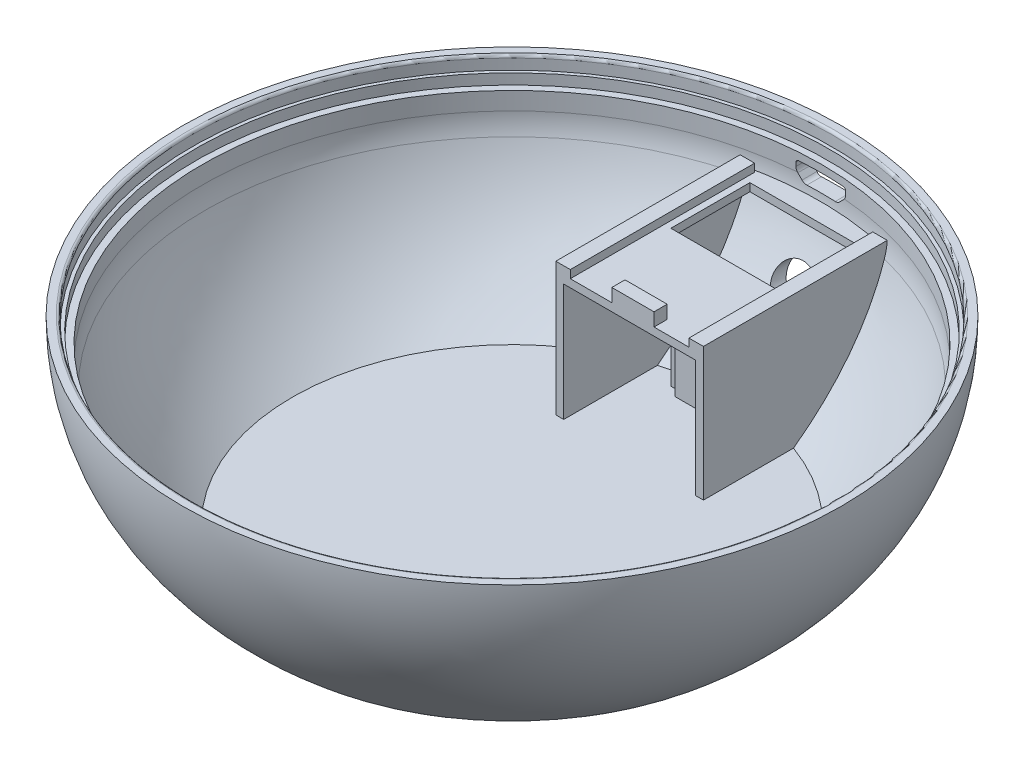
SolidWorks part; units mm, degrees
ref_plane "Plano frontal" through (0, 0, 0) normal (0, 0, 1) x (1, 0, 0)
ref_plane "Plano superior" through (0, 0, 0) normal (0, 1, 0) x (1, 0, 0)
ref_plane "Plano direito" through (0, 0, 0) normal (1, 0, 0) x (0, 0, -1)
sketch "Esboço1" plane through (0, 0, 0) normal (0, 0, 1) x (1, 0, 0)
  line L0 (0, 0) -> (0, -29.3333)
  line L1 (33.9935, -29.3333) -> (0, -29.3333)
  line L4 (0, 0) -> (50, 0)
  ellipse E0 centre (0, 0) end of major axis (-50, 0) minor radius 40 (33.9935, -29.3333) -> (50, 0) ccw
  dimension "D1" = 40
  dimension "D2" = 100
  dimension "D3" = 33.9935
revolve "Revolução1" add sketch "Esboço1" angle 360 about L0
shell "Casca1" thickness 2 removed face at (0, 0, 50)
sketch "Esboço7" plane through (0, 0, 0) normal (0, 1, 0) x (1, 0, 0)
  circle A0 centre (0, 0) radius 47
  circle A1 centre (0, 0) radius 48
  dimension "D1" = 94
extrude "Ressalto-extrusão3" add sketch "Esboço7" against normal up to next
sketch "Esboço9" plane through (0, 0, 0) normal (0, 1, 0) x (1, 0, 0)
  circle A0 centre (0, 0) radius 48.5
  dimension "D1" = 97
extrude "Corte-extrusão5" cut sketch "Esboço9" against normal blind 2
fillet "Filete3" radius 10 1 edges at (0, -7.7061, 47)
fillet "Filete4" radius 0.4 1 edges at (0, 0, 48.5)
fillet "Filete9" radius 6 1 edges at (0, -29.3333, 33.9935)
sketch "Esboço10" plane through (0, -2, 0) normal (0, 1, 0) x (1, 0, 0)
  circle A0 centre (0, 0) radius 48
  dimension "D1" = 96
extrude "Corte-extrusão6" cut sketch "Esboço10" against normal blind 1.6
sketch "Esboço15" plane through (0, 0, 0) normal (0, 0, 1) x (1, 0, 0)
  line L0 (0, -7.3333) -> (0, -4.7333) construction
  line L2 (-3.375, -4.7333) -> (3.375, -4.7333)
  line L3 (3.775, -5.1333) -> (3.775, -5.681)
  line L4 (3.4964, -6.3736) -> (2.8702, -7.0259)
  line L5 (2.1488, -7.3333) -> (-2.1488, -7.3333)
  line L6 (33.3248, -27.3333) -> (-33.3248, -27.3333) construction
  line L7 (-3.4964, -6.3736) -> (-2.8702, -7.0259)
  line L8 (-3.775, -5.1333) -> (-3.775, -5.681)
  arc A0 (2.8702, -7.0259) -> (2.1488, -7.3333) centre (2.1488, -6.3333) cw
  arc A1 (-2.8702, -7.0259) -> (-2.1488, -7.3333) centre (-2.1488, -6.3333) ccw
  arc A2 (3.775, -5.681) -> (3.4964, -6.3736) centre (2.775, -5.681) cw
  arc A3 (-3.4964, -6.3736) -> (-3.775, -5.681) centre (-2.775, -5.681) cw
  arc A4 (3.375, -4.7333) -> (3.775, -5.1333) centre (3.375, -5.1333) cw
  arc A5 (-3.775, -5.1333) -> (-3.375, -4.7333) centre (-3.375, -5.1333) cw
  point P14 (2.575, -7.3333)
  point P17 (-2.575, -7.3333)
  point P20 (3.775, -6.0833)
  point P23 (-3.775, -6.0833)
  point P26 (3.775, -4.7333)
  point P29 (-3.775, -4.7333)
  dimension "D6" = 1
  dimension "D7" = 0.4
  dimension "D1" = 7.55
  dimension "D2" = 2.6
  dimension "D3" = 1.35
  dimension "D4" = 5.15
  dimension "D5" = 20
extrude "Corte-extrusão9" cut sketch "Esboço15" against normal blind 62
ref_plane "Plano1" through (0, 0, -46.8482) normal (0, 0, -1) x (-1, 0, 0)
sketch "Esboço17" plane through (0, 0, -46.8482) normal (0, 0, -1) x (-1, 0, 0)
  line L0 (3.775, -5.681) -> (3.775, -5.1333) construction
  line L1 (11, -8.3333) -> (-11.4, -8.3333)
  line L2 (11, -8.3333) -> (11, -9.5333)
  line L3 (11, -9.5333) -> (-11.4, -9.5333)
  line L4 (-11.4, -8.3333) -> (-11.4, -9.5333)
  line L5 (-3.775, -5.1333) -> (-3.775, -5.681) construction
  line L7 (-3.375, -4.7333) -> (3.375, -4.7333) construction
  dimension "D1" = 1.2
  dimension "D2" = 7.225
  dimension "D3" = 22.4
  dimension "D4" = 3.6
  dimension "D5" = 7.625
extrude "Ressalto-extrusão4" add sketch "Esboço17" against normal blind 29.2
sketch "Esboço19" plane through (0, -9.5333, 0) normal (0, -1, 0) x (1, 0, 0)
  line L1 (-11, -17.6482) -> (-8.8, -17.6482)
  line L2 (-11, -17.6482) -> (-11, -45.6186)
  line L3 (-11, -45.6186) -> (-8.8, -45.6186)
  line L4 (-8.8, -17.6482) -> (-8.8, -45.6186)
  line L5 (11.4, -17.6482) -> (9.2, -17.6482)
  line L6 (11.4, -17.6482) -> (11.4, -45.5396)
  line L7 (11.4, -45.5396) -> (9.2, -45.5396)
  line L8 (9.2, -17.6482) -> (9.2, -45.5396)
  arc A0 (-11, -45.1386) -> (11.4, -45.0392) centre (0, 0) ccw construction
  dimension "D1" = 2.2
  dimension "D2" = 2.2
extrude "Ressalto-extrusão5" add sketch "Esboço19" against normal blind 2.4
sketch "Esboço20" plane through (0, -8.3333, 0) normal (0, 1, 0) x (1, 0, 0)
  line L0 (-8.8, 17.6482) -> (9.2, 17.6482) construction
  line L1 (-2.5, 17.6482) -> (3.9, 17.6482)
  line L2 (-2.5, 17.6482) -> (-2.5, 19.6482)
  line L3 (-2.5, 19.6482) -> (3.9, 19.6482)
  line L4 (3.9, 17.6482) -> (3.9, 19.6482)
  line L6 (-8.8, 17.6482) -> (-8.8, 45.6186) construction
  line L7 (9.2, 45.5396) -> (9.2, 17.6482) construction
  dimension "D1" = 2
  dimension "D2" = 6.3
  dimension "D3" = 6.4
  dimension "D4" = 5.3
extrude "Ressalto-extrusão6" add sketch "Esboço20" along normal blind 2
sketch "Esboço24" plane through (0, 0, 0) normal (0, 0, 1) x (1, 0, 0)
  line L1 (9.2, -27.3333) -> (11.4, -27.3333) construction
  ellipse E0 centre (0, -17.3333) end of major axis (-3, -17.3333) minor radius 2.5
  dimension "D1" = 10
  dimension "D2" = 6
  dimension "D3" = 2.5
extrude "Corte-extrusão12" cut sketch "Esboço24" against normal up to next
ref_plane "Plano2" through (0, -9.5333, 0) normal (0, -1, 0) x (-1, 0, 0)
sketch "Esboço29" plane through (0, -9.5333, 0) normal (0, -1, 0) x (-1, 0, 0)
  line L0 (0, 16.1333) -> (0, -16.1333) construction
  line L1 (4.4, 31.9) -> (-4.4, 31.9)
  line L2 (4.4, 31.9) -> (4.4, 29.1)
  line L3 (4.4, 29.1) -> (-4.4, 29.1)
  line L4 (-4.4, 31.9) -> (-4.4, 29.1)
  line L5 (4.4, 31.9) -> (-4.4, 29.1) construction
  line L6 (4.4, 29.1) -> (-4.4, 31.9) construction
  point P0 (0, 30.5)
  dimension "D3" = 30.5
  dimension "D1" = 8.8
  dimension "D2" = 2.8
extrude "Ressalto-extrusão11" add sketch "Esboço29" along normal up to surface and the other way up to next up to face at (0, -27.3333, 33.3248)
sketch "Esboço30" plane through (0, -8.3333, 0) normal (0, 1, 0) x (1, 0, 0)
  line L1 (-7.8, 43.9) -> (8.2, 43.9)
  line L2 (-7.8, 43.9) -> (-7.8, 31.9)
  line L3 (-7.8, 31.9) -> (8.2, 31.9)
  line L4 (8.2, 43.9) -> (8.2, 31.9)
  line L5 (-7.8, 43.9) -> (8.2, 31.9) construction
  line L6 (-7.8, 31.9) -> (8.2, 43.9) construction
  line L7 (-8.8, 17.6482) -> (-8.8, 45.6186) construction
  line L8 (-4.4, 31.9) -> (4.4, 31.9) construction
  line L9 (9.2, 45.5396) -> (9.2, 17.6482) construction
  point P0 (0.2, 37.9)
  dimension "D1" = 16
  dimension "D2" = 12
  dimension "D3" = 0
  dimension "D4" = 1
  dimension "D5" = 1
extrude "Corte-extrusão13" cut sketch "Esboço30" against normal blind 4
sketch "Esboço27" plane through (0, 0, 0) normal (1, 0, 0) x (0, 0, -1)
  line L0 (40.7485, -21.3333) -> (30.1545, -21.3333)
  line L1 (30.1545, -21.3333) -> (30.1545, -27.3333)
  line L2 (30.1545, -27.3333) -> (33.7166, -27.7767)
  line L4 (31.9, -27.3333) -> (29.1, -27.3333) construction
  line L5 (33.7166, -27.7767) -> (37.7706, -25.4136)
  line L6 (37.7706, -25.4136) -> (39.1733, -23.8825)
  line L7 (39.1733, -23.8825) -> (40.7485, -21.3333)
  line L8 (40.9291, -19.8333) -> (43.4209, -19.8333) construction
  dimension "D1" = 1.5
extrude "Ressalto-extrusão9" add sketch "Esboço27" along normal blind 6 and the other way blind 6
sketch "Esboço31" plane through (0, -9.5333, 0) normal (0, -1, 0) x (1, 0, 0)
  line L1 (-11, -17.6482) -> (-9.8, -17.6482)
  line L2 (-11, -17.6482) -> (-11, -45.4156)
  line L3 (-11, -45.4156) -> (-9.8, -45.4156)
  line L4 (-9.8, -17.6482) -> (-9.8, -45.4156)
  line L5 (11.4, -17.6482) -> (10.2, -17.6482)
  line L6 (11.4, -17.6482) -> (11.4, -45.3274)
  line L7 (11.4, -45.3274) -> (10.2, -45.3274)
  line L8 (10.2, -17.6482) -> (10.2, -45.3274)
  arc A0 (-11, -45.14) -> (11.4, -45.0406) centre (0, 0) ccw construction
  point P10 (0, 0)
  point P14 (0, 0)
  point P15 (0, 0)
  dimension "D1" = 1.2
  dimension "D4" = 1.2
extrude "Ressalto-extrusão12" add sketch "Esboço31" along normal up to next
